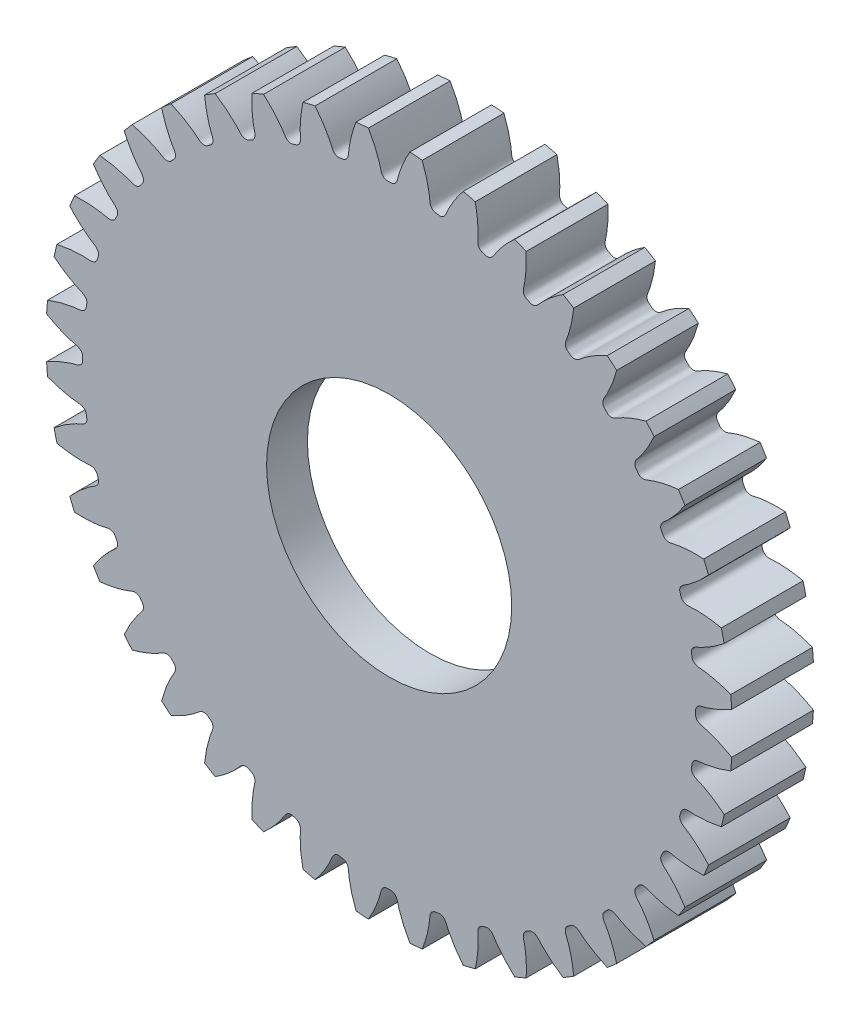
SolidWorks part; units mm, degrees
ref_plane "Alzado" through (0, 0, 0) normal (0, 0, 1) x (1, 0, 0)
ref_plane "Planta" through (0, 0, 0) normal (0, 1, 0) x (1, 0, 0)
ref_plane "Vista lateral" through (0, 0, 0) normal (1, 0, 0) x (0, 0, -1)
ref_axis "Eje1" through (0, 0, 55) along (0, 0, -1)
sketch "SketchRevolveEngranaje Grueso(8.3)" plane through (0, 0, 0) normal (1, 0, 0) x (0, 0, -1)
  line L0 (0, 0) -> (1, 0) construction
  line L1 (-0.5, 0) -> (-0.5, 4.2)
  line L2 (-0.5, 4.2) -> (0.5, 4.2)
  line L3 (0.5, 4.2) -> (0.5, 0)
  line L4 (0.5, 0) -> (-0.5, 0)
revolve "Engranaje Grueso(8.3)" add sketch "SketchRevolveEngranaje Grueso(8.3)" angle 360 about L0
sketch "SketchToothEngranaje Grueso(8.3)" plane through (0, 0, 0) normal (0, 0, 1) x (1, 0, 0)
  arc A0 (4.202, 0.2593) -> (4.202, -0.2593) centre (0, 0) cw
  spline S0 degree 3 poles (4.202, -0.2593) (4.1745, -0.2432) (4.138, -0.2231) (4.0923, -0.2) (4.0668, -0.1877) (4.0422, -0.1764) (4.0184, -0.166) (3.9955, -0.1564) (3.9736, -0.1477) (3.9527, -0.1398) (3.9327, -0.1327) (3.9137, -0.1263) (3.8957, -0.1205) (3.8788, -0.1155) (3.8629, -0.1111) (3.8451, -0.1064) (3.8308, -0.1033) (3.82, -0.1003) (3.8152, -0.0988) (3.8105, -0.0972) (3.8058, -0.0954) (3.8012, -0.0935) (3.7967, -0.0913) (3.7921, -0.0889) (3.7875, -0.0862) (3.7828, -0.0831) (3.7781, -0.0796) (3.7734, -0.0755) (3.7686, -0.0707) (3.7639, -0.0649) (3.7595, -0.0582) (3.7555, -0.0504) (3.7523, -0.0414) (3.7504, -0.032) (3.7496, -0.0181) (3.7503, 0) (3.7496, 0.0181) (3.7504, 0.032) (3.7523, 0.0414) (3.7555, 0.0504) (3.7595, 0.0582) (3.7639, 0.0649) (3.7686, 0.0707) (3.7734, 0.0755) (3.7781, 0.0796) (3.7828, 0.0831) (3.7875, 0.0862) (3.7921, 0.0889) (3.7967, 0.0913) (3.8012, 0.0935) (3.8058, 0.0954) (3.8105, 0.0972) (3.8152, 0.0988) (3.82, 0.1003) (3.8308, 0.1033) (3.8451, 0.1064) (3.8629, 0.1111) (3.8788, 0.1155) (3.8957, 0.1205) (3.9137, 0.1263) (3.9327, 0.1327) (3.9527, 0.1398) (3.9736, 0.1477) (3.9955, 0.1564) (4.0184, 0.166) (4.0422, 0.1764) (4.0668, 0.1877) (4.0923, 0.2) (4.138, 0.2231) (4.1745, 0.2432) (4.202, 0.2593) knots 0 0 0 0 0.086797 0.113582 0.139293 0.16393 0.187493 0.209982 0.231396 0.251737 0.271004 0.289197 0.306316 0.322361 0.337331 0.351228 0.372583 0.377176 0.381719 0.386232 0.390736 0.395262 0.399843 0.404521 0.409345 0.414376 0.419685 0.425356 0.43148 0.438152 0.445453 0.45343 0.462059 0.471223 0.479506 0.5 0.520494 0.528777 0.537941 0.54657 0.554547 0.561848 0.56852 0.574644 0.580315 0.585624 0.590655 0.595479 0.600157 0.604738 0.609264 0.613768 0.618281 0.622824 0.627417 0.648772 0.662669 0.677639 0.693684 0.710803 0.728996 0.748263 0.768604 0.790018 0.812507 0.83607 0.860707 0.886418 0.913203 1 1 1 1
extrude "ToothExtrudeCutEngranaje Grueso(8.3)" cut sketch "SketchToothEngranaje Grueso(8.3)" against normal blind 0.5 and the other way blind 0.5
pattern_circular "PatternEngranaje Grueso(8.3)" count 40 every 9 about axis through (0, 0, 55) along (0, 0, -1) of "ToothExtrudeCutEngranaje Grueso(8.3)"
sketch "AuxiliarySketchEngranaje Grueso(8.3)" plane through (0, 0, 0) normal (0, 0, 1) x (1, 0, 0)
  circle A0 centre (0, 0) radius 4 construction
  circle A1 centre (0, 0) radius 3.7588 construction
  circle A2 centre (0, 0) radius 3.8334 construction
  circle A3 centre (0, 0) radius 4.2 construction
  circle A4 centre (0, 0) radius 3.75 construction
  dimension "PitchDiameter" = 8
  dimension "BaseDiameter" = 7.5175
  dimension "FormDiameter" = 7.6667
  dimension "MajorDiameter" = 8.4
  dimension "MinorDiameter" = 7.5
sketch "Croquis5" plane through (0, 0, 0.5) normal (0, 0, 1) x (1, 0, 0)
  circle A0 centre (0, 0) radius 1.5
  dimension "D1" = 3
extrude "Cortar-Extruir2" cut sketch "Croquis5" against normal blind 10
sketch "Croquis6" plane through (0, 0, -0.5) normal (0, 0, -1) x (-1, 0, 0)
  circle A0 centre (0, 0) radius 2.75
  dimension "D1" = 5.5
extrude "Cortar-Extruir3" cut sketch "Croquis6" against normal blind 0.5
